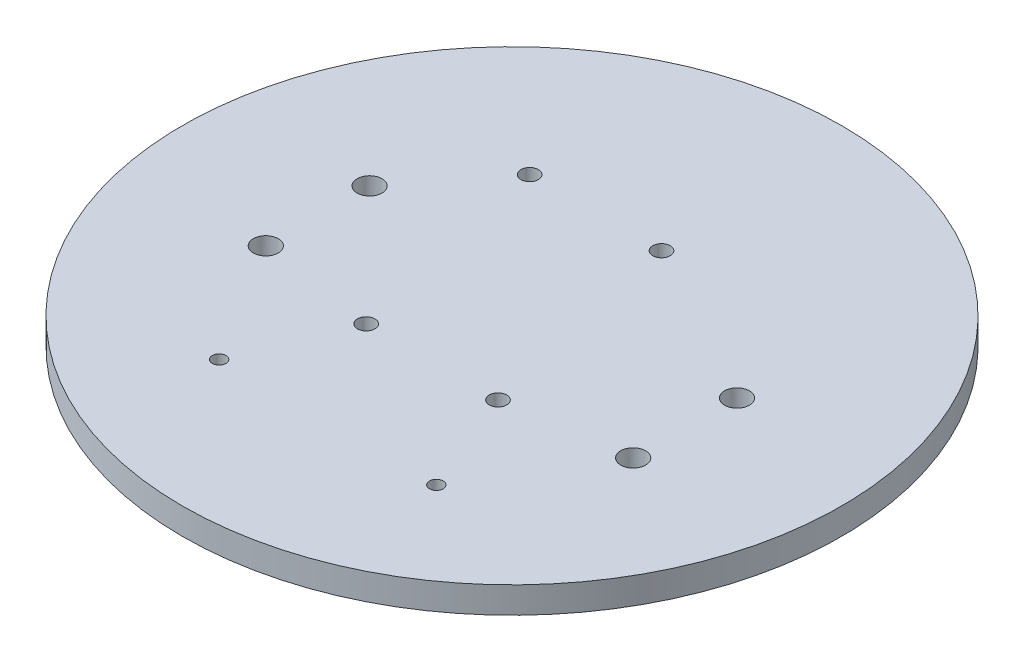
SolidWorks part; units mm, degrees
other "Markup1"
sketch "Sketch21" plane through (-65.5, -15.05, -60) normal (-0.0927, -0.2854, -0.9539) x (0.9951, -0.0609, -0.0785)
material "6061 Alloy"
ref_plane "Front Plane" through (0, 0, 0) normal (0, 0, 1) x (1, 0, 0)
ref_plane "Top Plane" through (0, 0, 0) normal (0, 1, 0) x (1, 0, 0)
ref_plane "Right Plane" through (0, 0, 0) normal (1, 0, 0) x (0, 0, -1)
sketch "Sketch1" plane through (0, 0, 0) normal (0, 1, 0) x (1, 0, 0)
  circle A0 centre (0, 0) radius 79.375
  dimension "D1" = 158.75
extrude "Boss-Extrude1" add sketch "Sketch1" along normal mid plane 6.35
sketch "Sketch2" plane through (0, -3.175, 0) normal (0, -1, 0) x (1, 0, 0)
  circle A0 centre (0, 0) radius 12.065
  circle A1 centre (0, 0) radius 79.375 construction
  dimension "D1" = 24.13
sketch "Sketch5" plane through (0, 3.175, 0) normal (0, 1, 0) x (1, 0, 0)
  circle A0 centre (0, 0) radius 10.4
  circle A1 centre (0, 0) radius 79.375 construction
  dimension "D1" = 20.8
hole_wizard "Tap Drill for M5x0.8 Tap1" positions "Sketch22" profile "Sketch23" hole size "M5x0.8" standard "ANSI Metric" end condition through all
sketch "Sketch22" plane through (0, 3.175, 0) normal (0, 1, 0) x (1, 0, 0)
  point P0 (-27.3188, 31.5712)
  point P3 (4.4312, 31.5712)
  point P6 (-15.875, -19.2459)
  point P9 (15.875, -19.2459)
  dimension "D1" = 31.75
  dimension "D2" = 31.5712
  dimension "D3" = 4.4312
  dimension "D4" = 31.75
  dimension "D5" = 19.2459
  dimension "D6" = 15.875
sketch "Sketch23" plane through (-27.3188, 3.175, -31.5712) normal (1, 0, 0) x (0, 0, 1)
  line L0 (0, 0) -> (0, 6.35)
  line L1 (0, 6.35) -> (2.1, 6.35)
  line L2 (2.1, 6.35) -> (2.1, 0)
  line L5 (2.1, 0) -> (0, 0)
  line L11 (0, -6.35) -> (0, 107.95) construction
  dimension "Thru Hole Dia." = 4.2
  dimension "Thru Hole Depth" = 6.35
hole_wizard "Tap Drill for M7x1.0 Tap1" positions "Sketch24" profile "Sketch25" hole size "M7x1.0" standard "ANSI Metric" end condition through all
sketch "Sketch24" plane through (0, 3.175, 0) normal (0, 1, 0) x (1, 0, 0)
  point P0 (-44.245, 9.9416)
  point P3 (-44.245, -15.0584)
  point P6 (44.245, 9.9416)
  point P9 (44.245, -15.0584)
  dimension "D1" = 25
  dimension "D2" = 44.245
  dimension "D3" = 9.9416
  dimension "D4" = 25
  dimension "D5" = 44.245
  dimension "D6" = 15.0584
sketch "Sketch25" plane through (-44.245, 3.175, -9.9416) normal (1, 0, 0) x (0, 0, 1)
  line L0 (0, 0) -> (0, 6.35)
  line L1 (0, 6.35) -> (3, 6.35)
  line L2 (3, 6.35) -> (3, 0)
  line L5 (3, 0) -> (0, 0)
  line L11 (0, -6.35) -> (0, 107.95) construction
  dimension "Thru Hole Dia." = 6
  dimension "Thru Hole Depth" = 6.35
hole_wizard "Tap Drill for M4x0.7 Tap1" positions "Sketch26" profile "Sketch27" hole size "M4x0.7" standard "ANSI Metric" end condition through all
sketch "Sketch26" plane through (0, 3.175, 0) normal (0, 1, 0) x (1, 0, 0)
  point P0 (-26.155, -44.3844)
  point P3 (26.155, -44.3844)
  dimension "D1" = 52.31
  dimension "D2" = 44.3844
  dimension "D3" = 26.155
sketch "Sketch27" plane through (-26.155, 3.175, 44.3844) normal (1, 0, 0) x (0, 0, 1)
  line L0 (0, 0) -> (0, 6.35)
  line L1 (0, 6.35) -> (1.65, 6.35)
  line L2 (1.65, 6.35) -> (1.65, 0)
  line L5 (1.65, 0) -> (0, 0)
  line L11 (0, -6.35) -> (0, 107.95) construction
  dimension "Thru Hole Dia." = 3.3
  dimension "Thru Hole Depth" = 6.35
